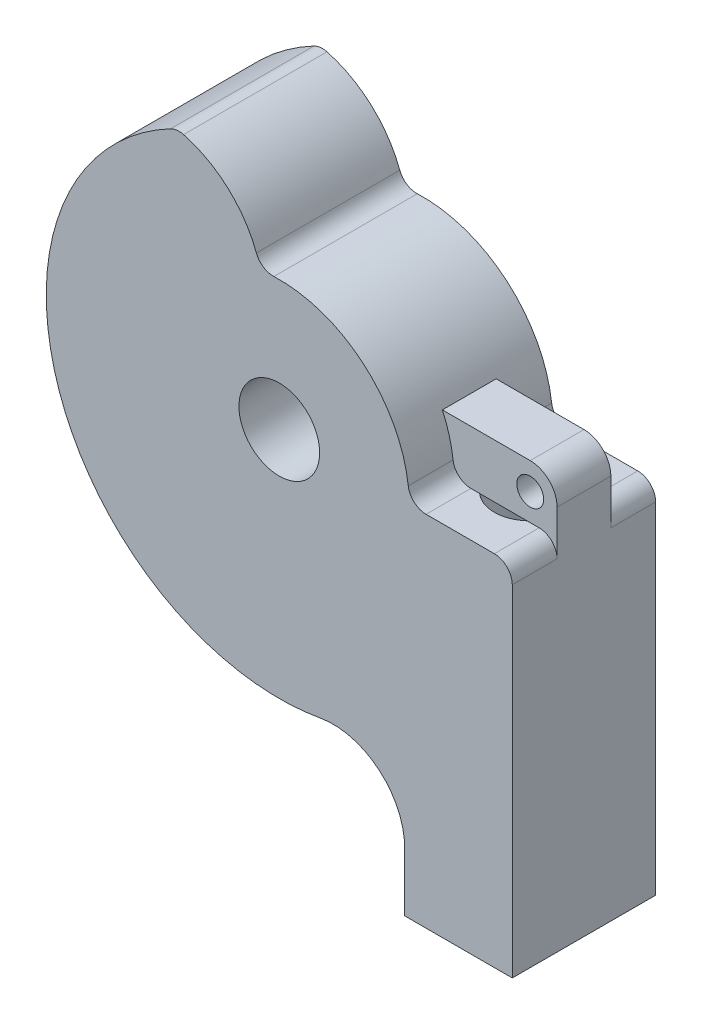
SolidWorks part; units mm, degrees
ref_plane "Front Plane" through (0, 0, 0) normal (0, 0, 1) x (1, 0, 0)
ref_plane "Top Plane" through (0, 0, 0) normal (0, 1, 0) x (1, 0, 0)
ref_plane "Right Plane" through (0, 0, 0) normal (1, 0, 0) x (0, 0, -1)
sketch "Sketch2" plane through (0, 0, 0) normal (0, 0, 1) x (1, 0, 0)
  line L0 (13, 0) -> (13, -20)
  line L1 (13, -20) -> (7, -20)
  line L2 (7, -20) -> (7, -10.9545)
  line L3 (10, 0) -> (10, -20) construction
  arc A0 (13, 0) -> (7, -10.9545) centre (0, 0) ccw
  circle A1 centre (0, 0) radius 10 construction
  dimension "Diameter" = 20
  dimension "Rod Holer Thickness" = 6
  dimension "Rod Holder Length" = 20
extrude "Boss-Extrude1" add sketch "Sketch2" along normal mid plane 8
hole_wizard "M4 Clearance Hole1" positions "Sketch3" profile "Sketch4" hole size "M4" standard "ANSI Metric" end condition up to next
sketch "Sketch3" plane through (0, 0, 4) normal (0, 0, 1) x (1, 0, 0)
  point P2 (0, 0)
sketch "Sketch4" plane through (0, 0, 4) normal (1, 0, 0) x (0, -1, 0)
  line L0 (0, 0) -> (0, 8)
  line L1 (0, 8) -> (2.25, 8)
  line L2 (2.25, 8) -> (2.25, 0)
  line L5 (2.25, 0) -> (0, 0)
  line L11 (0, -6.35) -> (0, 107.95) construction
  dimension "Thru Hole Dia." = 4.5
  dimension "Thru Hole Depth" = 8
sketch "Sketch5" plane through (0, -20, 0) normal (0, -1, 0) x (1, 0, 0)
  line L0 (13, 4) -> (7, -4) construction
  circle A0 centre (10, 0) radius 2
  dimension "Rod Hole Diameter" = 4
extrude "Cut-Extrude1" cut sketch "Sketch5" against normal blind 20
ref_axis "Axis1" through (10, 0, 0) along (0, -1, 0)
sketch "Sketch8" plane through (0, 0, -4) normal (0, 0, 1) x (1, 0, 0)
  line L0 (0, 0) -> (-21.8723, 0) construction
  line L1 (0, 0) -> (-6.8944, 5.7851) construction
  circle A0 centre (-6.8944, 5.7851) radius 3
  dimension "D2" = 6
  dimension "D1" = 40
  dimension "D3" = 9
extrude "Cut-Extrude3" cut sketch "Sketch8" along normal offset from surface (6.4 mm away) 1.6 up to face at (2.25, 0, 4)
sketch "Sketch9" plane through (0, 0, 4) normal (0, 0, 1) x (1, 0, 0)
  line L1 (13, 0) -> (7.25, 0)
  line L2 (13, 0) -> (13, 10.075) construction
  arc A0 (13, 0) -> (7, -10.9545) centre (0, 0) ccw construction
  arc A1 (7.25, 0) -> (-1.057, 7.1725) centre (0, 0) ccw
  circle A2 centre (0, 0) radius 2.25 construction
  arc A4 (-1.057, 7.1725) -> (-5.7272, 11.6705) centre (-6.8944, 5.7851) ccw
  circle A5 centre (-6.8944, 5.7851) radius 3 construction
  arc A6 (13, 0) -> (-5.7272, 11.6705) centre (0, 0) ccw
  dimension "D1" = 5
  dimension "D2" = 3
extrude "Cut-Extrude4" cut sketch "Sketch9" against normal through all
sketch "Sketch6" plane through (0, 0, 0) normal (0, 0, 1) x (1, 0, 0)
  line L4 (13, 1.5) -> (13, 0)
  line L6 (11.5, 3) -> (6.6002, 3)
  line L8 (7.25, 0) -> (13, 0) construction
  line L9 (7.25, 0) -> (13, 0)
  arc A2 (13, 1.5) -> (11.5, 3) centre (11.5, 1.5) ccw
  arc A3 (7.25, 0) -> (-1.057, 7.1725) centre (0, 0) ccw construction
  arc A4 (7.25, 0) -> (6.6002, 3) centre (0, 0) ccw
  dimension "Spring Attchment Diameter" = 1.5
extrude "Boss-Extrude2" add sketch "Sketch6" along normal mid plane 3
fillet "Fillet1" radius 1 6 edges at (-5.7272, 11.6705, 0) (7.25, 0, 2.75) (7.25, 0, -2.75) (-1.057, 7.1725, 0) (13, 0, -2.75) (13, 0, 2.75)
sketch "Sketch7" plane through (0, 0, 1.5) normal (0, 0, 1) x (1, 0, 0)
  circle A0 centre (11.5, 1.5) radius 0.75
  arc A1 (13, 1.5) -> (11.5, 3) centre (11.5, 1.5) ccw construction
  dimension "Spring Hole Diam" = 1.5
extrude "Cut-Extrude2" cut sketch "Sketch7" against normal through all both and the other way through all
fillet "Fillet2" radius 4 1 edges at (7, -10.9545, 0)
sketch "Sketch10" [suppressed] plane through (0, 0, -3) normal (0, 0, -1) x (-1, 0, 0)
  line L0 (-7, -10.9545) -> (-7, -20) construction
  line L1 (-7, -10.9545) -> (-7, -20)
  line L2 (-7, -20) -> (-1.5, -20)
  line L3 (-1.5, -20) -> (-1.5, -12.9132)
  arc A0 (-7, -10.9545) -> (6.0647, 11.4987) centre (0, 0) ccw construction
  arc A1 (-7, -10.9545) -> (-1.5, -12.9132) centre (0, 0) ccw
  circle A2 centre (-4.6, -16.5) radius 1.5
  dimension "D1" = 3
  dimension "D3" = 2
  dimension "D4" = 1.6
  dimension "D2" = 5.5
extrude "Boss-Extrude3" [suppressed] add sketch "Sketch10" against normal up to surface (6 mm away) up to face at (2.25, 0, 4)
fillet "Fillet3" [suppressed] radius 2
